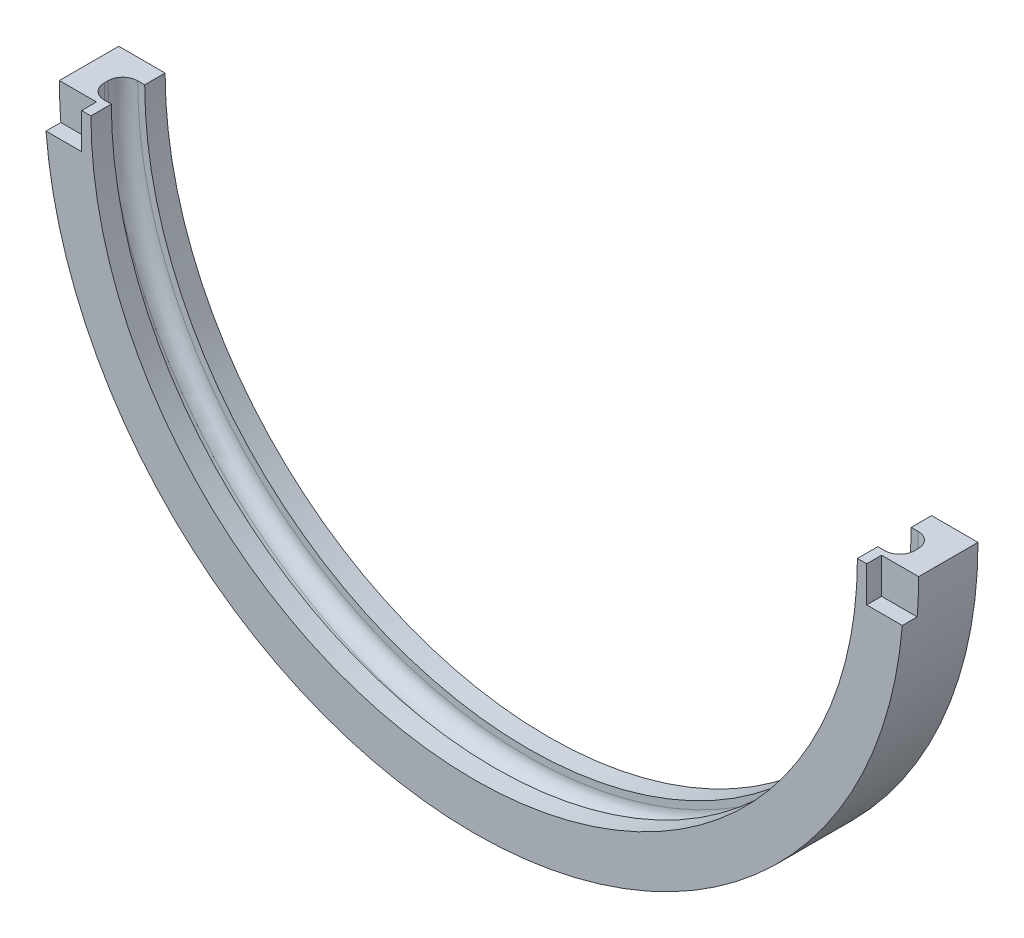
SolidWorks part; units mm, degrees
ref_plane "Front Plane" through (0, 0, 0) normal (0, 0, 1) x (1, 0, 0)
ref_plane "Top Plane" through (0, 0, 0) normal (0, 1, 0) x (1, 0, 0)
ref_plane "Right Plane" through (0, 0, 0) normal (1, 0, 0) x (0, 0, -1)
sketch "Sketch1" plane through (0, 0, 0) normal (0, 0, 1) x (1, 0, 0)
  line L0 (-69.342, 73.533) -> (-73.533, 73.533)
  line L1 (69.342, 73.533) -> (73.533, 73.533)
  circle A0 centre (0, 73.533) radius 73.533
  circle A1 centre (0, 73.533) radius 69.342
  dimension "D1" = 147.066
  dimension "D2" = 138.684
extrude "Boss-Extrude1" add sketch "Sketch1" along normal blind 5.715 contours A1 L0 A0 L1 region at (0, 2.5468, 0)
sketch "Sketch3" plane through (0, 0, 5.715) normal (0, 0, 1) x (1, 0, 0)
  line L0 (-65.5955, 73.533) -> (-73.533, 73.533)
  line L1 (65.5955, 73.533) -> (73.533, 73.533)
  circle A0 centre (0, 73.533) radius 73.533
  circle A1 centre (0, 73.533) radius 65.5955
  arc M3 (69.342, 73.533) -> (-69.342, 73.533) centre (0, 73.533) cw
  line M4 (-69.342, 73.533) -> (-73.533, 73.533)
  arc M5 (-73.533, 73.533) -> (73.533, 73.533) centre (0, 73.533) ccw
  line M6 (73.533, 73.533) -> (69.342, 73.533)
  dimension "D1" = 131.191
extrude "Boss-Extrude2" add sketch "Sketch3" along normal blind 3.4925 contours A1 L0 L1 M3 | M6 M3 M4 M5 region at (0, 6.387, 5.715) region at (0, 2.5468, 5.715)
sketch "Sketch4" plane through (0, 0, 0) normal (0, 0, -1) x (-1, 0, 0)
  line L0 (-65.5955, 73.533) -> (-73.533, 73.533)
  line L1 (65.5955, 73.533) -> (73.533, 73.533)
  circle A0 centre (0, 73.533) radius 73.533
  circle A1 centre (0, 73.533) radius 65.5955
  arc M3 (69.342, 73.533) -> (-69.342, 73.533) centre (0, 73.533) cw
  line M4 (-69.342, 73.533) -> (-73.533, 73.533)
  arc M5 (-73.533, 73.533) -> (73.533, 73.533) centre (0, 73.533) ccw
  line M6 (73.533, 73.533) -> (69.342, 73.533)
extrude "Boss-Extrude3" add sketch "Sketch4" along normal blind 3.4925 contours A1 L0 L1 M3 | M6 M3 M4 M5 region at (0, 6.387, 0) region at (0, 2.5468, 0)
fillet "Fillet1" radius 2.54 2 edges at (0, 4.191, 5.715) (0, 4.191, 0)
sketch "Sketch5" plane through (0, 0, 0) normal (0, 1, 0) x (1, 0, 0)
  line L0 (64.2819, -2.8575) -> (-64.2819, -2.8575) construction
  circle A0 centre (0, -2.8575) radius 1.524
  dimension "D1" = 3.048
extrude "Cut-Extrude1" [suppressed] cut sketch "Sketch5" along normal blind 6.35
sketch "Sketch6" plane through (0, 0, 9.2075) normal (0, 0, 1) x (1, 0, 0)
  line L0 (-65.5955, 73.533) -> (-73.533, 73.533) construction
  line L1 (-67.1839, 73.533) -> (-73.8294, 73.533)
  line L2 (-67.1839, 73.533) -> (-67.1839, 67.437)
  line L3 (-67.1839, 67.437) -> (-73.8294, 67.437)
  line L4 (-73.8294, 73.533) -> (-73.8294, 67.437)
  line L5 (0, 10.7538) -> (0, 95.14) construction
  line L18 (67.1839, 67.437) -> (73.8294, 67.437)
  line L19 (73.8294, 73.533) -> (73.8294, 67.437)
  line L20 (67.1839, 73.533) -> (73.8294, 73.533)
  line L21 (67.1839, 73.533) -> (67.1839, 67.437)
  dimension "D1" = 6.096
extrude "Cut-Extrude5" cut sketch "Sketch6" against normal blind 2.54
